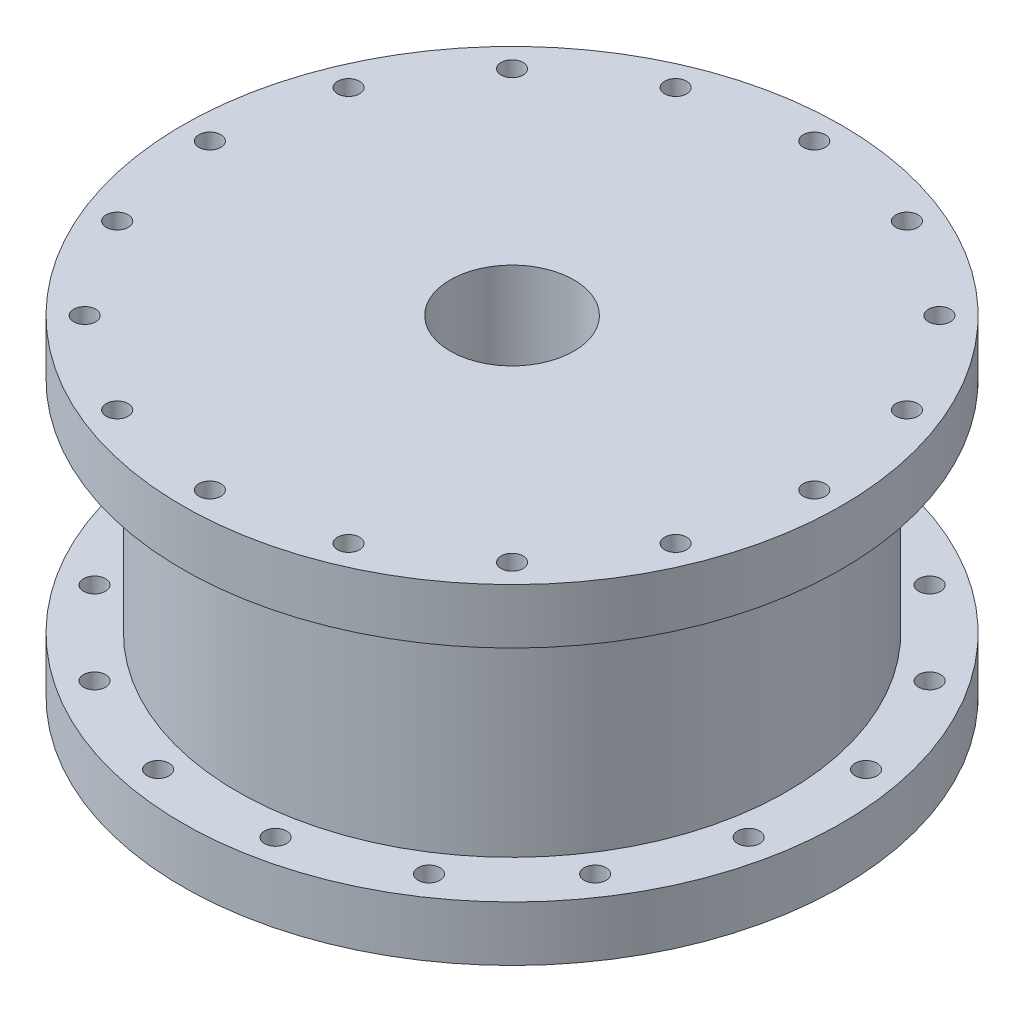
SolidWorks part; units mm, degrees
ref_plane "Front Plane" through (0, 0, 0) normal (0, 0, 1) x (1, 0, 0)
ref_plane "Top Plane" through (0, 0, 0) normal (0, 1, 0) x (1, 0, 0)
ref_plane "Right Plane" through (0, 0, 0) normal (1, 0, 0) x (0, 0, -1)
sketch "Sketch3" plane through (0, 0, 0) normal (1, 0, 0) x (0, 0, -1)
  line L0 (0, 0) -> (0, 30)
  line L1 (0, 30) -> (29.972, 30)
  line L2 (29.972, 30) -> (29.972, 25)
  line L3 (29.972, 25) -> (24.9933, 25)
  line L4 (24.9933, 25) -> (24.9933, 5)
  line L5 (24.9933, 5) -> (29.972, 5)
  line L6 (29.972, 5) -> (29.972, 0)
  line L7 (29.972, 0) -> (0, 0)
  line L8 (0, 0) -> (0.0836, -0.1672)
  line L9 (0, 30) -> (0, 51.4239) construction
  dimension "D1" = 5
  dimension "Hub_Width" = 20
  dimension "Hub Radius" = 29.972
revolve "Revolve1" add sketch "Sketch3" angle 360 about L9 region at (0, 15, -13.4298)
sketch "Sketch4" plane through (0, 30, 0) normal (0, 1, 0) x (1, 0, 0)
  circle A0 centre (0, 0) radius 5.6215
extrude "Cut-Extrude1" cut sketch "Sketch4" against normal through all
sketch "Sketch5" plane through (0, 25, 0) normal (0, -1, 0) x (1, 0, 0)
  line L0 (0, 0) -> (0, 27.4827) construction
  line L1 (-8.2189, 28.8231) -> (-7.5363, 26.4292) construction
  line L2 (-7.5363, 26.4292) -> (-6.8536, 24.0352) construction
  circle A0 centre (0, 27.4827) radius 1
  circle A1 centre (0, 0) radius 24.9933 construction
  circle A2 centre (0, 0) radius 27.4827 construction
  circle A3 centre (0, 0) radius 29.972 construction
  dimension "D1" = 2
extrude "Cut-Extrude2" cut sketch "Sketch5" against normal through all
pattern_circular "CirPattern2" count 16 over 360 about axis through (0, 0, 0) along (0, 1, 0) of "Cut-Extrude2"
sketch "Sketch7" plane through (0, 0, 0) normal (0, -1, 0) x (1, 0, 0)
  line L0 (0, 0) -> (-5.8472, 29.3961) construction
  line L1 (-10.5172, 25.3907) -> (-5.3411, 26.8515) construction
  line L2 (-5.3411, 26.8515) -> (0, 27.4827) construction
  circle A0 centre (0, 0) radius 29.972 construction
  circle A1 centre (0, 0) radius 29.972 construction
  circle A2 centre (-5.3411, 26.8515) radius 1
  circle A3 centre (-10.5172, 25.3907) radius 1 construction
  circle A4 centre (0, 27.4827) radius 1 construction
  circle A5 centre (-10.5172, 25.3907) radius 1 construction
  circle A6 centre (0, 27.4827) radius 1 construction
  circle A7 centre (0, 0) radius 27.4827 construction
  dimension "D1" = 2
extrude "Cut-Extrude3" cut sketch "Sketch7" against normal up to next
pattern_circular "CirPattern3" count 16 over 360 about axis through (0, 0, 0) along (0, 1, 0) of "Cut-Extrude3"
equation "\"Spoke hole diameter\"= \"D1@Sketch5\""
